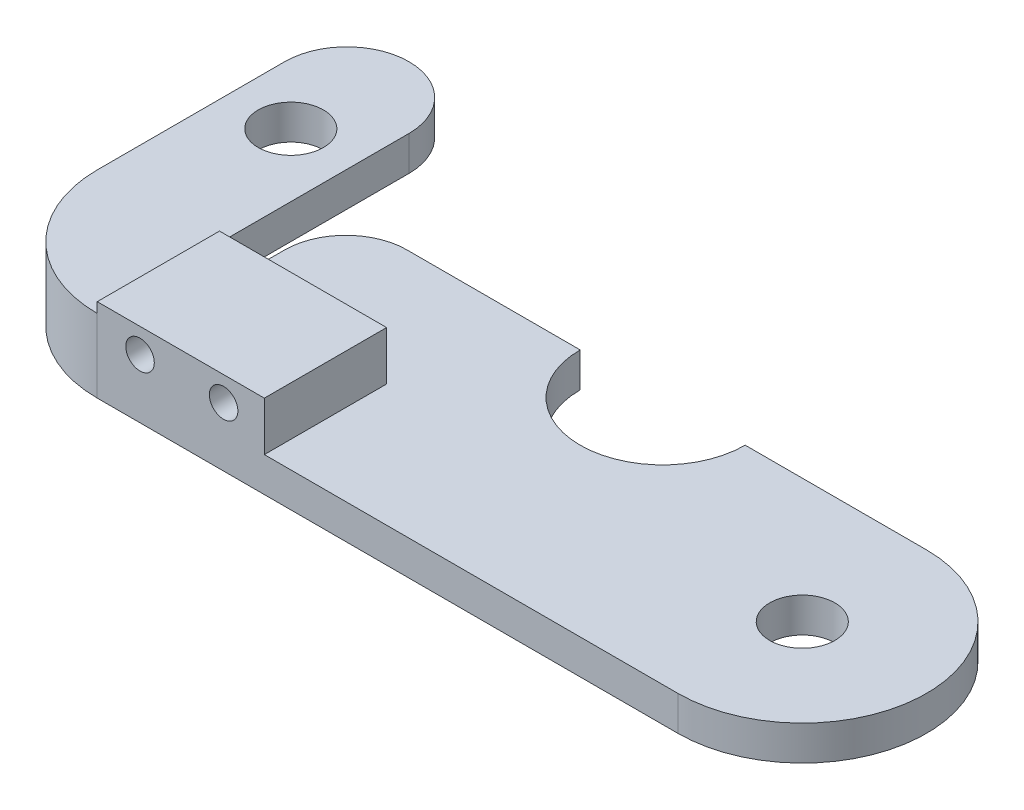
SolidWorks part; units mm, degrees
ref_plane "Front Plane" through (0, 0, 0) normal (0, 0, 1) x (1, 0, 0)
ref_plane "Top Plane" through (0, 0, 0) normal (0, 1, 0) x (1, 0, 0)
ref_plane "Right Plane" through (0, 0, 0) normal (1, 0, 0) x (0, 0, -1)
sketch "Sketch1" plane through (0, 0, 0) normal (0, 1, 0) x (1, 0, 0)
  line L0 (-13.6869, -1.9274) -> (14.8131, -1.9274)
  line L1 (14.8131, -1.9274) -> (14.8131, 4.1726) construction
  line L2 (14.8131, 10.2726) -> (5.9131, 10.2726)
  line L3 (-13.6869, 7.2726) -> (-13.6869, 4.1726)
  line L4 (-2.1869, 10.2726) -> (-10.6869, 10.2726)
  line L5 (-13.6869, 4.1726) -> (-19.7869, 4.1726) construction
  line L6 (-13.6869, 4.1726) -> (-13.6869, -1.9274)
  arc A0 (14.8131, -1.9274) -> (14.8131, 10.2726) centre (14.8131, 4.1726) ccw
  circle A1 centre (14.8131, 4.1726) radius 1.6
  arc A2 (-10.6869, 10.2726) -> (-13.6869, 7.2726) centre (-10.6869, 7.2726) ccw
  arc A3 (-2.1869, 10.2726) -> (5.9131, 10.2726) centre (1.8631, 10.2726) ccw
  arc A4 (-19.7869, 4.1726) -> (-13.6869, -1.9274) centre (-13.6869, 4.1726) ccw construction
  point P0 (0, 0)
  dimension "D3" = 3.2
  dimension "D4" = 6
  dimension "D5" = 8.1
  dimension "D1" = 28.5
  dimension "D2" = 6.1
  dimension "D6" = 6.1
  dimension "D7" = 11.5
extrude "Boss-Extrude1" add sketch "Sketch1" along normal blind 1.7
sketch "Sketch2" plane through (0, 1.7, 0) normal (0, 1, 0) x (1, 0, 0)
  line L1 (-13.6869, -1.9274) -> (-5.4869, -1.9274)
  line L2 (-13.6869, -1.9274) -> (-13.6869, 4.0726)
  line L3 (-13.6869, 4.0726) -> (-5.4869, 4.0726)
  line L4 (-5.4869, -1.9274) -> (-5.4869, 4.0726)
  dimension "D1" = 8.2
  dimension "D2" = 6
extrude "Boss-Extrude2" add sketch "Sketch2" along normal blind 2.4
sketch "Sketch3" plane through (0, 0, 1.9274) normal (0, 0, 1) x (1, 0, 0)
  line L0 (-5.4869, 4.1) -> (-5.4869, 1.7) construction
  line L1 (-13.6869, 4.1) -> (-5.4869, 4.1) construction
  circle A0 centre (-11.5869, 2.9) radius 0.7
  circle A1 centre (-7.4869, 2.9) radius 0.7
  dimension "D1" = 1.4
  dimension "D2" = 1.4
  dimension "D3" = 2
  dimension "D4" = 4.1
  dimension "D5" = 1.2
extrude "Cut-Extrude1" cut sketch "Sketch3" against normal up to surface (6 mm away) up to face at (-9.5869, 2.9, -4.0726)
ref_plane "Plane1" through (0, 1.9, 0) normal (0, 1, 0) x (1, 0, 0)
sketch "Sketch4" plane through (0, 0, 0) normal (0, -1, 0) x (1, 0, 0)
  line L0 (-13.6869, 1.9274) -> (-13.6869, -4.1726)
  line L2 (-13.6869, -4.1726) -> (-19.7869, -4.1726)
  arc A0 (-13.6869, 1.9274) -> (-19.7869, -4.1726) centre (-13.6869, -4.1726) ccw
  dimension "D1" = 6.1
extrude "Boss-Extrude3" add sketch "Sketch4" against normal blind 3.6 separate body
sketch "Sketch5" plane through (0, 0, -4.1726) normal (0, 0, -1) x (-1, 0, 0)
  line L0 (19.7869, 3.6) -> (19.7869, 0) construction
  line L1 (13.6869, 3.6) -> (19.7869, 3.6)
  line L2 (13.6869, 3.6) -> (13.6869, 1.9)
  line L3 (13.6869, 1.9) -> (19.7869, 1.9)
  line L4 (19.7869, 3.6) -> (19.7869, 1.9)
  line L5 (2.1869, 1.7) -> (10.6869, 1.7) construction
  dimension "D1" = 0.2
extrude "Boss-Extrude4" add sketch "Sketch5" along normal blind 9.2
sketch "Sketch6" plane through (0, 3.6, 0) normal (0, 1, 0) x (1, 0, 0)
  line L0 (-19.7869, 13.3726) -> (-13.6869, 13.3726) construction
  line L1 (-19.7869, 13.3726) -> (-13.6869, 13.3726)
  arc A0 (-13.6869, 13.3726) -> (-19.7869, 13.3726) centre (-16.7369, 13.3726) ccw
extrude "Boss-Extrude5" add sketch "Sketch6" against normal up to surface (1.7 mm away) up to face at (-16.7369, 1.9, -8.7726)
sketch "Sketch7" plane through (0, 3.6, 0) normal (0, 1, 0) x (1, 0, 0)
  line L0 (-19.7869, 13.3726) -> (-19.7869, 4.1726) construction
  circle A0 centre (-16.7869, 10.6726) radius 1.6
  arc A2 (-13.6869, 13.3726) -> (-19.7869, 13.3726) centre (-16.7369, 13.3726) ccw construction
  dimension "D2" = 3.2
  dimension "D1" = 3
  dimension "D3" = 2.7
extrude "Cut-Extrude2" cut sketch "Sketch7" against normal up to surface (1.7 mm away) up to face at (-16.7369, 1.9, -9.5351)
